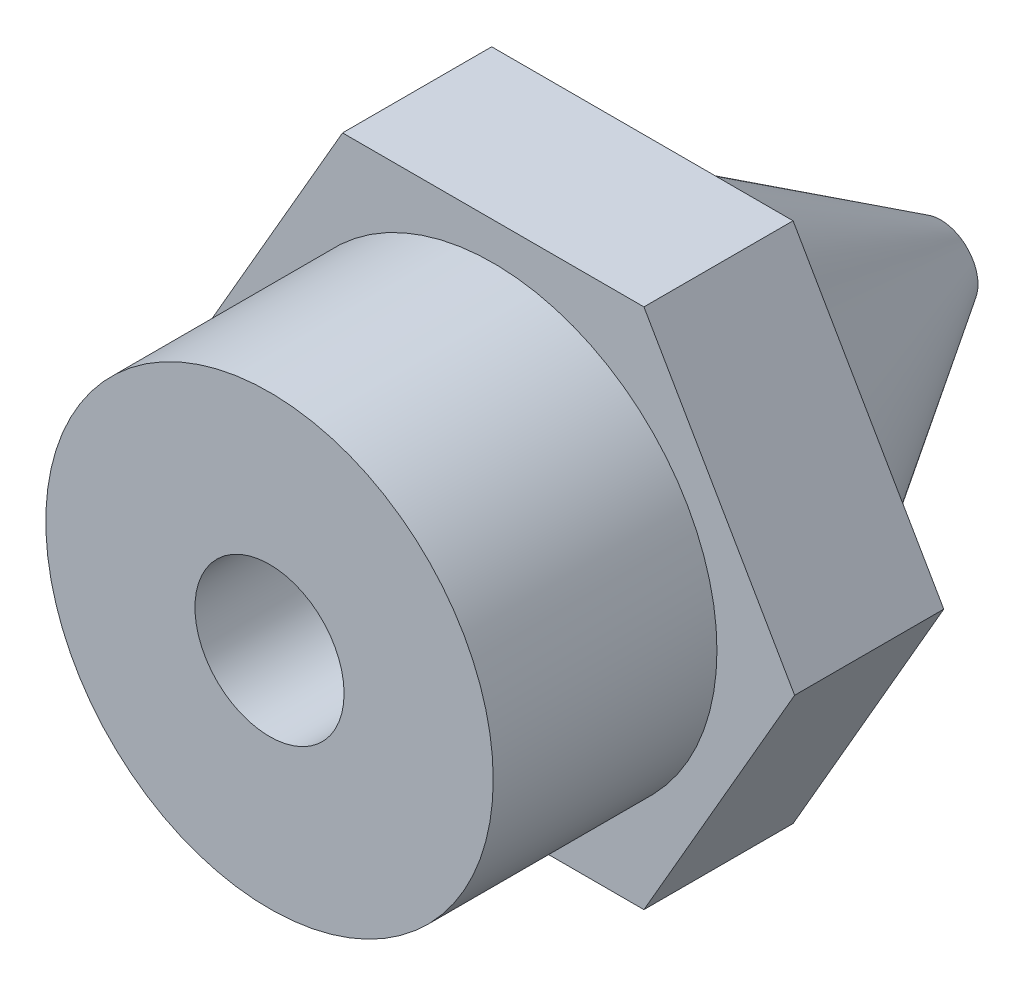
SolidWorks part; units mm, degrees
ref_plane "Plan de face" through (0, 0, 0) normal (0, 0, 1) x (1, 0, 0)
ref_plane "Plan de dessus" through (0, 0, 0) normal (0, 1, 0) x (1, 0, 0)
ref_plane "Plan de droite" through (0, 0, 0) normal (1, 0, 0) x (0, 0, -1)
sketch "Esquisse1" plane through (0, 0, 0) normal (0, 0, 1) x (1, 0, 0)
  line L1 (4.0415, 0) -> (2.0207, 3.5)
  line L2 (2.0207, 3.5) -> (-2.0207, 3.5)
  line L3 (-2.0207, 3.5) -> (-4.0415, 0)
  line L4 (-4.0415, 0) -> (-2.0207, -3.5)
  line L5 (-2.0207, -3.5) -> (2.0207, -3.5)
  line L6 (2.0207, -3.5) -> (4.0415, 0)
  circle A0 centre (0, 0) radius 3.5 construction
  dimension "D1" = 7
extrude "Boss.-Extru.1" add sketch "Esquisse1" along normal blind 9 contours L3 L4 L5 L6 L1 L2
sketch "Esquisse2" plane through (0, 0, 9) normal (0, 0, 1) x (1, 0, 0)
  line L1 (-9.4849, 6.2226) -> (10.1391, 6.2226)
  line L2 (-9.4849, 6.2226) -> (-9.4849, -9.3115)
  line L3 (-9.4849, -9.3115) -> (10.1391, -9.3115)
  line L4 (10.1391, 6.2226) -> (10.1391, -9.3115)
  circle A0 centre (0, 0) radius 3
  dimension "D1" = 6
extrude "Enlèv. mat.-Extru.1" cut sketch "Esquisse2" against normal blind 3
cosmetic thread "Représentation de filetage1" parameters "D1"=3, "D2"=4.891
sketch "Esquisse3" plane through (0, 0, 0) normal (0, 0, -1) x (-1, 0, 0)
  line L1 (5.6434, -6.9413) -> (-5.6238, -6.9413)
  line L2 (5.6434, -6.9413) -> (5.6434, 7.0198)
  line L3 (5.6434, 7.0198) -> (-5.6238, 7.0198)
  line L4 (-5.6238, -6.9413) -> (-5.6238, 7.0198)
  circle A0 centre (0, 0) radius 3
  dimension "D1" = 6
extrude "Enlèv. mat.-Extru.2" cut sketch "Esquisse3" against normal blind 4
chamfer "Chanfrein1" distance 4 angle 32 1 edges at (-3, 0, 0) first distance on face at (-3, 0, 4)
sketch "Esquisse4" plane through (0, 0, 0) normal (0, 1, 0) x (1, 0, 0)
  line L0 (0, -9.4046) -> (0, 0.4979) construction
  line L1 (0, -9) -> (1, -9)
  line L2 (-3, -9) -> (3, -9) construction
  line L3 (0, 0) -> (0.2, 0)
  line L4 (0.2, 0) -> (0.2, -0.5)
  line L5 (0.2, -0.5) -> (1, -1.6425)
  line L6 (1, -9) -> (1, -1.6425)
  line L7 (0, -9) -> (0, 0)
  dimension "D1" = 1
  dimension "D2" = 0.2
  dimension "D3" = 0.5
revolve "Enlèvement de matière-Révolution1" cut sketch "Esquisse4" angle 360 about L0
